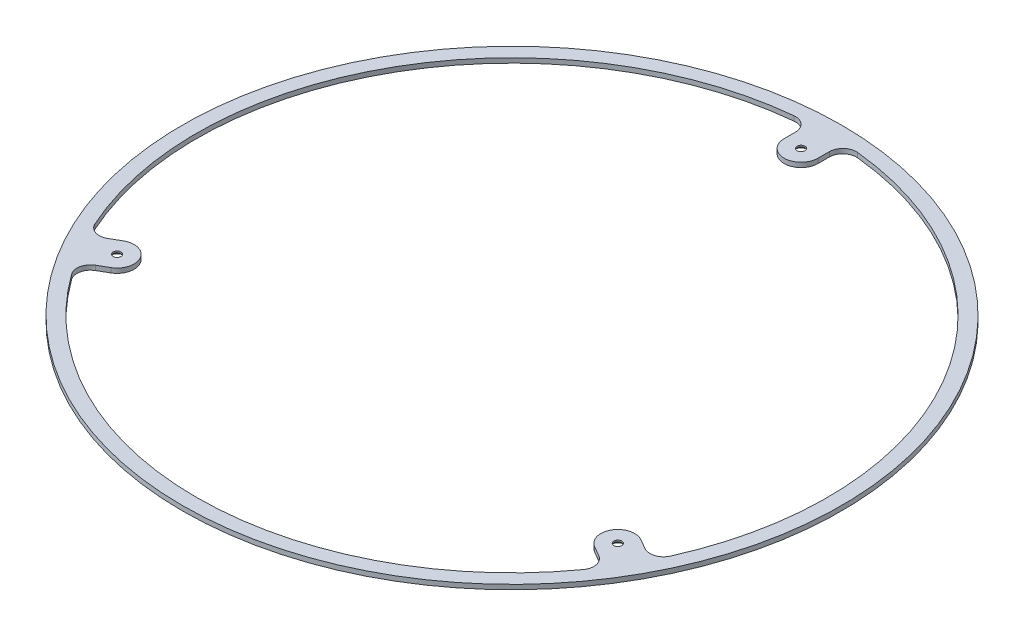
SolidWorks part; units mm, degrees
ref_plane "Front Plane" through (0, 0, 0) normal (0, 0, 1) x (1, 0, 0)
ref_plane "Top Plane" through (0, 0, 0) normal (0, 1, 0) x (1, 0, 0)
ref_plane "Right Plane" through (0, 0, 0) normal (1, 0, 0) x (0, 0, -1)
sketch "Sketch1" plane through (0, 0, 0) normal (0, 1, 0) x (1, 0, 0)
  circle A0 centre (0, 0) radius 146
  circle A1 centre (0, 0) radius 139.75
  dimension "D1" = 292
  dimension "D2" = 279.5
extrude "Boss-Extrude1" add sketch "Sketch1" along normal blind 2.07
sketch "Sketch2" plane through (0, 0, 0) normal (0, 1, 0) x (1, 0, 0)
  line L0 (-7.5, 128.0625) -> (-7.5, 139.5486)
  line L1 (7.5, 128.0625) -> (7.5, 139.5486)
  circle A0 centre (0, 0) radius 128.0625 construction
  circle A1 centre (0, 128.0625) radius 1.75
  arc A2 (-7.5, 128.0625) -> (7.5, 128.0625) centre (0, 128.0625) ccw
  circle A5 centre (0, 0) radius 139.75 construction
  arc A6 (7.5, 139.5486) -> (-7.5, 139.5486) centre (0, 0) ccw
  point P3 (0, 128.0625)
  dimension "D1" = 256.125
  dimension "D2" = 3.5
  dimension "D3" = 15
extrude "Boss-Extrude2" add sketch "Sketch2" along normal up to surface (2.07 mm away) up to face at (0, 2.07, 146)
sketch "Sketch4" plane through (0, 0, 0) normal (0, -1, 0) x (1, 0, 0)
  circle A0 centre (0, -128.0625) radius 1.75 construction
  circle A1 centre (0, -128.0625) radius 1.75
hole_wizard "CSK for M3 Countersunk Flat Head Screw1" positions "3DSketch1" profile "Sketch5" countersink size "M3" standard "DIN" end condition through all
sketch3d "3DSketch1"
  point P0 (0, 0, -128.0625)
sketch "Sketch5" plane through (0, 0, -128.0625) normal (1, 0, 0) x (0, 0, -1)
  line L0 (0, 0) -> (0, 2.07)
  line L1 (0, 2.07) -> (1.7, 2.07)
  line L2 (1.7, 2.07) -> (1.7, 1.45)
  line L3 (1.7, 1.45) -> (3.15, 0)
  line L5 (3.15, 0) -> (0, 0)
  line L6 (-1.7, 1.45) -> (-3.15, 0) construction
  line L11 (0, -6.35) -> (0, 107.95) construction
  dimension "Thru Hole Dia." = 3.4
  dimension "Thru Hole Depth" = 2.07
  dimension "Near C'Sink Dia." = 6.3
  dimension "Near C'Sink Angle" = 90
fillet "Fillet1" radius 6 2 edges at (-7.5, 1.035, -139.5486) (7.5, 1.035, -139.5486)
pattern_circular "CirPattern1" count 3 over 360 about axis through (0, 0, 0) along (0, 1, 0) of "Boss-Extrude2", "CSK for M3 Countersunk Flat Head Screw1", "Fillet1"
equation "\"head_mount_circle_diameter\"= 250mm * 1.0245"
equation "\"D1@Sketch2\"=\"head_mount_circle_diameter\""
